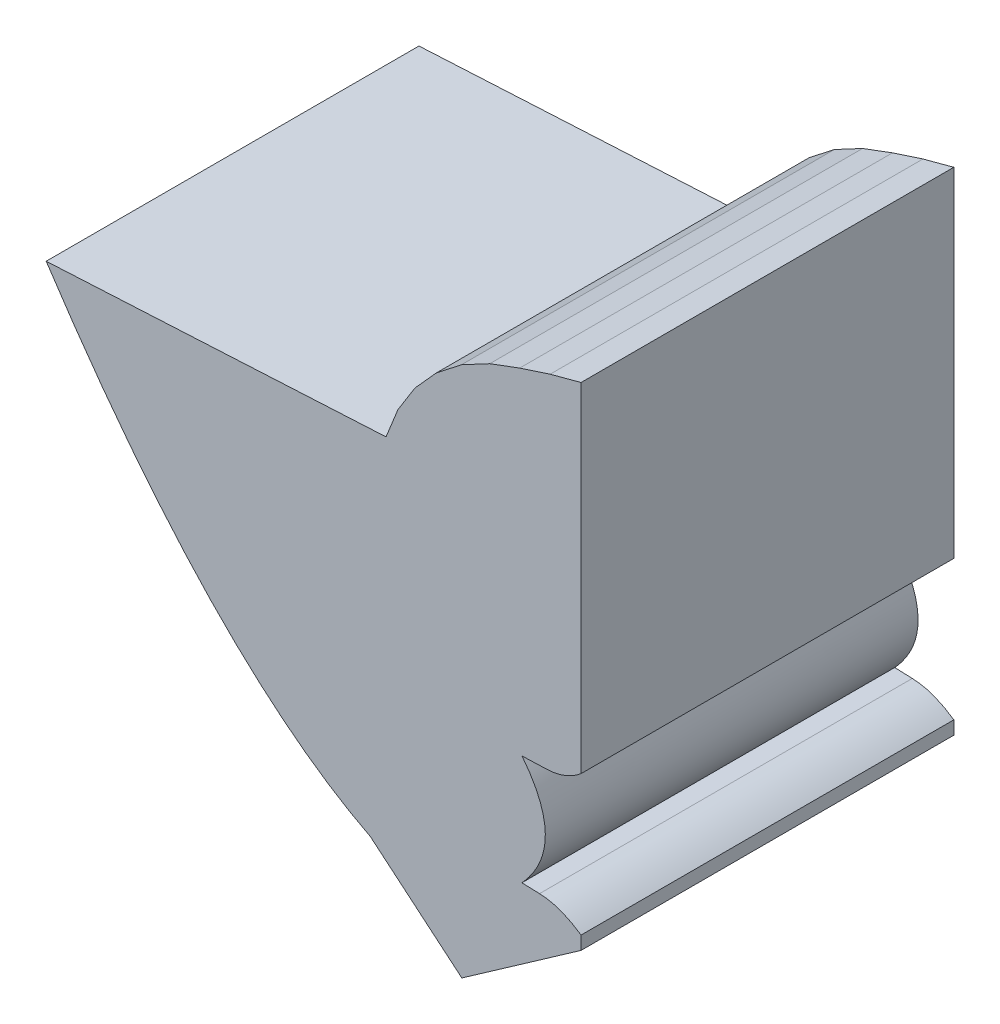
SolidWorks part; units mm, degrees
ref_plane "Alzado" through (0, 0, 0) normal (0, 0, 1) x (1, 0, 0)
ref_plane "Planta" through (0, 0, 0) normal (0, 1, 0) x (1, 0, 0)
ref_plane "Vista lateral" through (0, 0, 0) normal (1, 0, 0) x (0, 0, -1)
sketch "Croquis1" plane through (0, 0, 0) normal (0, 0, 1) x (1, 0, 0)
  line L0 (-8.9818, 12.6082) -> (-23.0359, 11.8716) construction
  line L1 (-8.9818, 12.6082) -> (-23.0359, 11.8716)
  line L2 (-8.9818, 12.6082) -> (-23.0359, 11.8716) construction
  line L3 (-2.1773, 6.1864) -> (-2.1773, -4.6845)
  line L4 (-8.9818, 12.6082) -> (-23.0359, 11.8716)
  line L6 (-1.3949, 1.9763) -> (0.3551, 2.2848) construction
  line L7 (-1.3949, 1.9763) -> (0.3551, 2.2848) construction
  line L8 (0.3551, 2.2848) -> (0.3551, 2.8423) construction
  line L9 (0.3551, 2.2848) -> (0.3551, 3.0015) construction
  line L10 (0.3551, -2.2848) -> (-1.3949, -2.2237) construction
  line L11 (0.3551, -2.2848) -> (-1.3949, -2.2237) construction
  line L12 (0.3551, 2.2848) -> (0.3551, -2.2848) construction
  line L13 (0.3551, -2.2848) -> (0.3551, -2.7233) construction
  line L14 (-8.9818, 12.6082) -> (-6.9949, 10.4774)
  line L15 (-23.0359, 11.5401) -> (-23.0359, 11.8716) construction
  line L16 (-23.0359, 11.5401) -> (-23.0359, 11.8716)
  arc A0 (-18.9452, 7.5409) -> (-23.0359, 11.5401) centre (-69.8841, -40.4718) ccw construction
  arc A1 (-18.9452, 7.5409) -> (-23.0359, 11.5401) centre (-69.8841, -40.4718) ccw
  spline S1 degree 2 poles (-4119.0151, 24659.0515) (3413.1083, -24757.661) (-2705.4818, 24835.5983) knots 0.405517 0.405517 0.405517 0.594449 0.594449 0.594449 weights 1 1 1 only from (-18.9452, 7.5409) to (-2.8466, -5.0591) construction
  spline S2 degree 2 poles (-18.9452, 7.5409) (-10.215, -3.6976) (-2.8466, -5.0591) knots 0.497667 0.497667 0.497667 0.499554 0.499554 0.499554 weights 1 1 1
  spline S3 degree 2 poles (-23607.9882, 8212.1168) (23492.4763, -8550.6979) (-23372.6553, 8887.1675) knots 0.40552 0.40552 0.40552 0.594498 0.594498 0.594498 weights 1 1 1 only from (0.3551, 3.0015) to (-6.9949, 10.4774) construction
  spline S4 degree 2 poles (-2.1773, 6.1864) (-4.0633, 8.1416) (-6.9949, 10.4774) knots 0.501383 0.501383 0.501383 0.502013 0.502013 0.502013 weights 1 1 1
  spline S5 degree 2 poles (-1.3949, -2.2237) (-0.9075, -0.1237) (-1.3949, 1.9763) knots 0 0 0 1 1 1 weights 1 3.231801 1 construction
  spline S6 degree 2 poles (-1.3949, -2.2237) (-0.9075, -0.1237) (-1.3949, 1.9763) knots 0 0 0 1 1 1 weights 1 3.231801 1 construction
  spline S7 degree 2 poles (-24934.0908, 1769.912) (24899.5391, -2178.5787) (-24858.838, 2586.1022) knots 0.405518 0.405518 0.405518 0.594474 0.594474 0.594474 weights 1 1 1 only from (-2.8466, -5.0591) to (0.3551, -2.7233) construction
  spline S8 degree 2 poles (-2.8466, -5.0591) (-2.4982, -4.873) (-2.1773, -4.6845) knots 0.498812 0.498812 0.498812 0.498912 0.498912 0.498912 weights 1 1 1
extrude "croquis base" add sketch "Croquis1" along normal mid plane 13.9874 contours S2 S8 L13 L11 S6 L7 L9 S4 L14 L1 L16 A1 region at (-10.1535, 5.1597, 0)
sketch "Croquis6" plane through (0, 0, 0) normal (1, 0, 0) x (0, 0, -1)
  line L0 (6.9937, 12.6082) -> (6.9937, 10.4774) construction
  line L1 (6.9937, 12.6082) -> (6.9937, -5.0591)
  line L2 (-6.9937, 12.6082) -> (-6.9937, 10.4774) construction
  line L3 (-6.9937, 12.6082) -> (-6.9937, -5.0591)
  line L4 (-6.9937, -5.0591) -> (6.9937, -5.0591) construction
  line L5 (-6.9937, -5.0591) -> (-4.9937, -5.0591)
  line L6 (6.9937, 12.6082) -> (4.9937, -5.0591)
  line L7 (-6.9937, 12.6082) -> (-4.9937, -5.0591)
  line L8 (4.9937, -5.0591) -> (6.9937, -5.0591)
  dimension "D1" = 2
  dimension "D2" = 2
sketch "Croquis9" plane through (0, 0, 0) normal (0, 0, 1) x (1, 0, 0)
  line L0 (0, 0) -> (-4.9559, 0) construction
  line L1 (-2.4454, 0.1046) -> (-1.25, 0) construction
  line L2 (-1.25, 0) -> (-1.25, -4.2203) construction
  line L3 (-2.1773, -1.8404) -> (-2.1773, -4.3883)
  line L4 (-2.1773, 6.1864) -> (-2.1773, -4.6845) construction
  line L5 (-2.4454, 0.1046) -> (-2.0532, -4.3783) construction
  line L6 (-2.4454, 0.1046) -> (-15.184, 3.0892) construction
  line L7 (-19.6099, 15.4015) -> (-15.184, 3.0892) construction
  line L9 (-15.184, 3.0892) -> (-25.9078, 12.6462) construction
  line L10 (-15.184, 3.0892) -> (-13.3572, 5.139) construction
  line L11 (-19.9694, 9.4938) -> (-10.3098, 10)
  line L12 (-10.3098, 10) -> (-2.1773, 6.0829)
  line L13 (-2.1773, 6.0829) -> (-2.1773, 2.4242)
  line L15 (-2.1773, 6.1864) -> (-2.1773, -4.6845) construction
  parabola Q0 (-2.1773, 2.4242) -> (-2.1773, -1.8404) focus (-2.4454, 0.1046) apex (-1.25, 0)
  parabola Q1 (-2.1773, -4.3883) -> (-19.9694, 9.4938) focus (-2.4454, 0.1046) apex (-2.0532, -4.3783)
  spline S0 degree 2 poles (-18.9452, 7.5409) (-10.215, -3.6976) (-2.8466, -5.0591) knots 0.497667 0.497667 0.497667 0.499554 0.499554 0.499554 weights 1 1 1 construction
  dimension "D1" = 95
  dimension "D2" = 1.25
  dimension "D3" = 1.2
  dimension "D4" = 4.5
  dimension "D5" = 5
  dimension "D6" = 3
  dimension "D7" = 10
extrude "lente ppal 1" add sketch "Croquis9" along normal up to surface and the other way up to surface contours Q1 L3 Q0 L13 L12 L11 region at (-9.1064, 3.5992, 0) up to face at (-11.7662, 6.8113, 6.9937) other way up to face at (-11.7662, 6.8113, -6.9937)
extrude "lente ppal 2" cut sketch "Croquis9<3>" against normal through all both and the other way through all flip side to cut
sketch "Croquis9<3>" plane through (0, 0, 0) normal (0, 0, 1) x (1, 0, 0) same geometry as "Croquis9"
sketch "Croquis8" plane through (0, 0, 0) normal (0, 0, 1) x (1, 0, 0)
  line L0 (-8.9818, 12.6082) -> (-23.0359, 11.8716) construction
  line L1 (-10.3098, 10) -> (0.1, 15.5879) construction
  line L3 (0.1, 2.8777) -> (0.1, 15.5879)
  line L5 (-7.2179, 10.162) -> (-6.7684, 11.2747)
  line L6 (-6.7684, 11.2747) -> (-6.1325, 12.2923)
  line L7 (-6.1325, 12.2923) -> (-5.3295, 13.1841)
  line L8 (-5.3295, 13.1841) -> (-4.3839, 13.9229)
  line L9 (-4.3839, 13.9229) -> (-3.3244, 14.4863)
  line L10 (-3.3244, 14.4863) -> (-2.2004, 14.9065)
  line L11 (-2.2004, 14.9065) -> (-1.0591, 15.2773)
  line L12 (-1.0591, 15.2773) -> (0.1, 15.5879)
  line L13 (-0.5, 2) -> (-9.2621, 13.0152) construction
  line L14 (-9.2621, 13.0152) -> (-9.6721, 13.4466) construction
  line L15 (-9.2621, 13.0152) -> (-9.8313, 13.8617) construction
  line L16 (-0.5, 2) -> (-6.9932, 10.7183) construction
  line L17 (-6.9932, 10.7183) -> (-9.8657, 11.8789) construction
  line L18 (-0.5, 2) -> (-6.4504, 11.7835) construction
  line L19 (-1.1905, 2.3769) -> (-13.6677, 1.9412) construction
  line L20 (-6.4504, 11.7835) -> (-8.5297, 13.0828) construction
  line L21 (-0.5, 2) -> (-5.731, 12.7382) construction
  line L22 (-0.5, 2) -> (-4.8567, 13.5535) construction
  line L23 (-4.8567, 13.5535) -> (-7.2264, 16.5865) construction
  line L24 (-0.5, 2) -> (-3.8542, 14.2046) construction
  line L25 (-3.8542, 14.2046) -> (-5.6175, 17.521) construction
  line L26 (-0.5, 2) -> (-2.7624, 14.6964) construction
  line L27 (-2.7624, 14.6964) -> (-4.1395, 18.3795) construction
  line L28 (-0.5, 2) -> (-1.6297, 15.0919) construction
  line L29 (-1.6297, 15.0919) -> (-2.365, 17.3548) construction
  line L30 (-0.5, 2) -> (-0.4796, 15.4326) construction
  line L31 (-0.4796, 15.4326) -> (-1.0837, 17.6873) construction
  line L32 (-6.4504, 11.7835) -> (-9.194, 13.4978) construction
  line L33 (-5.731, 12.7382) -> (-8.3325, 15.0806) construction
  line L34 (-10.3098, 10) -> (-10.3098, 19.2428) construction
  line L35 (-0.4796, 15.4326) -> (-1.3923, 18.839) construction
  line L36 (-10.3098, 10) -> (-7.2179, 10.162)
  line L37 (-6.9932, 10.7183) -> (-7.7178, 13.8573) construction
  line L38 (-6.9932, 10.7183) -> (-7.6851, 10.9979) construction
  line L39 (-6.4504, 11.7835) -> (-7.328, 15.5847) construction
  line L40 (-6.4504, 11.7835) -> (-8.1247, 12.8297) construction
  line L41 (-5.731, 12.7382) -> (-6.4786, 15.9764) construction
  line L42 (-5.731, 12.7382) -> (-7.1919, 14.0536) construction
  line L43 (-4.8567, 13.5535) -> (-5.8037, 17.6554) construction
  line L44 (-4.8567, 13.5535) -> (-6.0786, 15.1174) construction
  line L45 (-3.8542, 14.2046) -> (-4.8235, 18.4032) construction
  line L46 (-3.8542, 14.2046) -> (-4.9673, 16.2982) construction
  line L47 (-2.7624, 14.6964) -> (-3.6965, 18.7423) construction
  line L48 (-2.7624, 14.6964) -> (-3.4418, 16.5134) construction
  line L49 (-0.5, 2) -> (-0.5437, 2.5) construction
  line L50 (-0.5437, 2.5) -> (-0.8858, 3.4397) construction
  line L51 (0, 0) -> (0, 1.5958) construction
  line L52 (0, 12.6082) -> (0, -5.0591) construction
  line L53 (-1.6297, 15.0919) -> (-2.8173, 18.7468) construction
  line L54 (-1.6297, 15.0919) -> (-2.2911, 17.9567) construction
  line L55 (-0.4796, 15.4326) -> (-1.0428, 17.8722) construction
  line L56 (-10.3098, 10) -> (-2.1773, 2.3425)
  line L57 (-2.1773, 2.3425) -> (-1.1905, 2.3769)
  line L58 (-10.3098, 10) -> (-19.9694, 9.4938) construction
  line L60 (-2.1773, 6.0829) -> (-10.3098, 10) construction
  parabola Q0 (-1.1905, 2.3769) -> (0.1, 2.8777) focus (-0.8858, 3.4397) apex (-0.5437, 2.5)
  spline S1 degree 2 poles (-10.3098, 10) (-2.4445, 4.1882) (-0.2283, 0.4324) knots 0.500548 0.500548 0.500548 0.502013 0.502013 0.502013 weights 1 1 1 construction
  dimension "D1" = 5.039
  dimension "D3" = 15
  dimension "D4" = 25
  dimension "D5" = 80
  dimension "D6" = 45
  dimension "D7" = 35
  dimension "D8" = 7.5
  dimension "D9" = 5
  dimension "D10" = 55
  dimension "D11" = 211.322
  dimension "D12" = 206.691
  dimension "D13" = 202.027
  dimension "D14" = 197.339
  dimension "D15" = 192.633
  dimension "D16" = 0.5
  dimension "D17" = 0.5
  dimension "D18" = 2
  dimension "D19" = 5
  dimension "D20" = 20
  dimension "D21" = 88
  dimension "D22" = 1
  dimension "D23" = 0.1
  dimension "D24" = 178
  dimension "D25" = 1.2
  dimension "D26" = 10
extrude "lente frontal" add sketch "Croquis8" along normal up to surface and the other way up to surface up to face at (-5.0154, 2.8272, 6.9937) other way up to face at (-7.9808, 4.4301, -6.9937)
sketch "Croquis11" plane through (0, 0, 0) normal (0, 0, 1) x (1, 0, 0)
  line L0 (0, 0) -> (0, -3.4622) construction
  line L1 (0, 0) -> (3.4097, 0) construction
  line L2 (0, 0) -> (-1.5, -1.8) construction
  line L4 (-1.5209, -2.9998) -> (-1.5, -1.8) construction
  line L5 (-1.4581, -1.8011) -> (-2.5935, -1.7614) construction
  line L7 (0.1, -2.3678) -> (0.1, -2.8678)
  line L8 (0.1, 2.8777) -> (0.1, 15.5879) construction
  line L14 (-1.4581, -1.8011) -> (-9.7212, -1.5125)
  line L15 (-9.7212, -1.5125) -> (-4.3732, -6)
  line L16 (-4.3732, -6) -> (-4.3732, 3.7291) construction
  line L17 (0.1, -2.8678) -> (-4.3732, -6)
  parabola Q0 (-1.4581, -1.8011) -> (0.1, -2.3678) focus (-1.5209, -2.9998) apex (-1.5, -1.8)
  dimension "D1" = 1.8
  dimension "D2" = 88
  dimension "D3" = 1.2
  dimension "D4" = 1.5
  dimension "D5" = 1
  dimension "D6" = 0.5
  dimension "D7" = 6
  dimension "D9" = 105
  dimension "D10" = 55
extrude "lente trasera" add sketch "Croquis11" along normal up to surface and the other way up to surface up to face at (-3.7041, 8.4573, 6.9937) other way up to face at (-4.8085, 9.1371, -6.9937)
